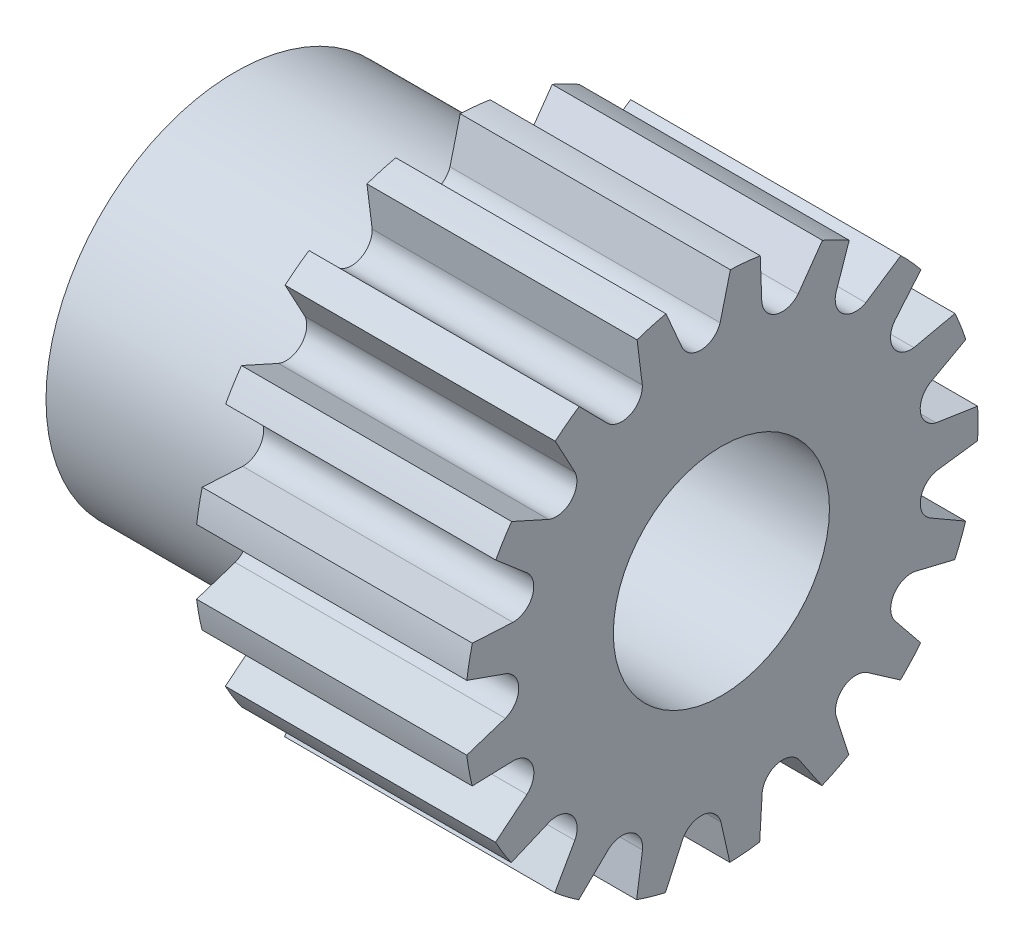
SolidWorks part; units mm, degrees
ref_plane "Спереди" through (0, 0, 0) normal (0, 0, 1) x (1, 0, 0)
ref_plane "Сверху" through (0, 0, 0) normal (0, 1, 0) x (1, 0, 0)
ref_plane "Справа" through (0, 0, 0) normal (1, 0, 0) x (0, 0, -1)
sketch "Эскиз1" plane through (0, 0, 0) normal (0, 0, 1) x (1, 0, 0)
  line L0 (0, 0) -> (18, 0) construction
  line L1 (18, 0) -> (18, 9.5)
  line L2 (18, 9.5) -> (8, 9.5)
  line L3 (8, 9.5) -> (8, 7)
  line L4 (8, 7) -> (0, 7)
  line L5 (0, 7) -> (0, 0)
  line L6 (0, 0) -> (18, 0)
  dimension "D1" = 18
  dimension "D2" = 10
  dimension "D3" = 9.5
  dimension "D4" = 7
revolve "Повернуть1" add sketch "Эскиз1" angle 360 about L0
sketch "Эскиз2" plane through (0, 0, 0) normal (-1, 0, 0) x (0, 0, 1)
  circle A0 centre (0, 0) radius 4
  dimension "D1" = 8
extrude "Вырез-Вытянуть1" cut sketch "Эскиз2" against normal blind 20
sketch "Эскиз3" plane through (8, 0, 0) normal (-1, 0, 0) x (0, 0, 1)
  line L0 (0.0463, 7.9839) -> (-0.3324, 9.4942)
  line L1 (1.4557, 7.8975) -> (2.052, 9.2757)
  line L6 (0, 0) -> (0.7686, 8.2278) construction
  line L7 (0.7686, 8.2278) -> (0.9159, 9.8046) construction
  arc A1 (2.052, 9.2757) -> (-0.3324, 9.4942) centre (0, 0) ccw
  arc A3 (0.0463, 7.9839) -> (1.4557, 7.8975) centre (0.7686, 8.2278) ccw
  dimension "D1" = 1.3783
  dimension "D2" = 9.5
  dimension "D4" = 8.2278
  dimension "D5" = 0.7624
  dimension "D3" = 37.471
extrude "Вырез-Вытянуть2" cut sketch "Эскиз3" against normal blind 10
ref_axis "Ось1" through (18, 0, 0) along (-1, 0, 0)
pattern_circular "Круговой массив1" count 17 over 360 about axis through (18, 0, 0) along (-1, 0, 0) of "Вырез-Вытянуть2"
sketch "Эскиз4" plane through (0, 0, 0) normal (0, 1, 0) x (1, 0, 0)
  line L0 (0, 7) -> (0, -7) construction
  circle A0 centre (4, 0) radius 2
  dimension "D1" = 4
  dimension "D2" = 4
extrude "Вырез-Вытянуть3" cut sketch "Эскиз4" against normal blind 10
sketch "Эскиз5" plane through (0, 0, 0) normal (0, 0, 1) x (1, 0, 0)
  line L0 (0, 7) -> (0, -7) construction
  circle A0 centre (4, 0) radius 2
  dimension "D1" = 4
  dimension "D2" = 4
extrude "Вырез-Вытянуть4" cut sketch "Эскиз5" against normal blind 10
